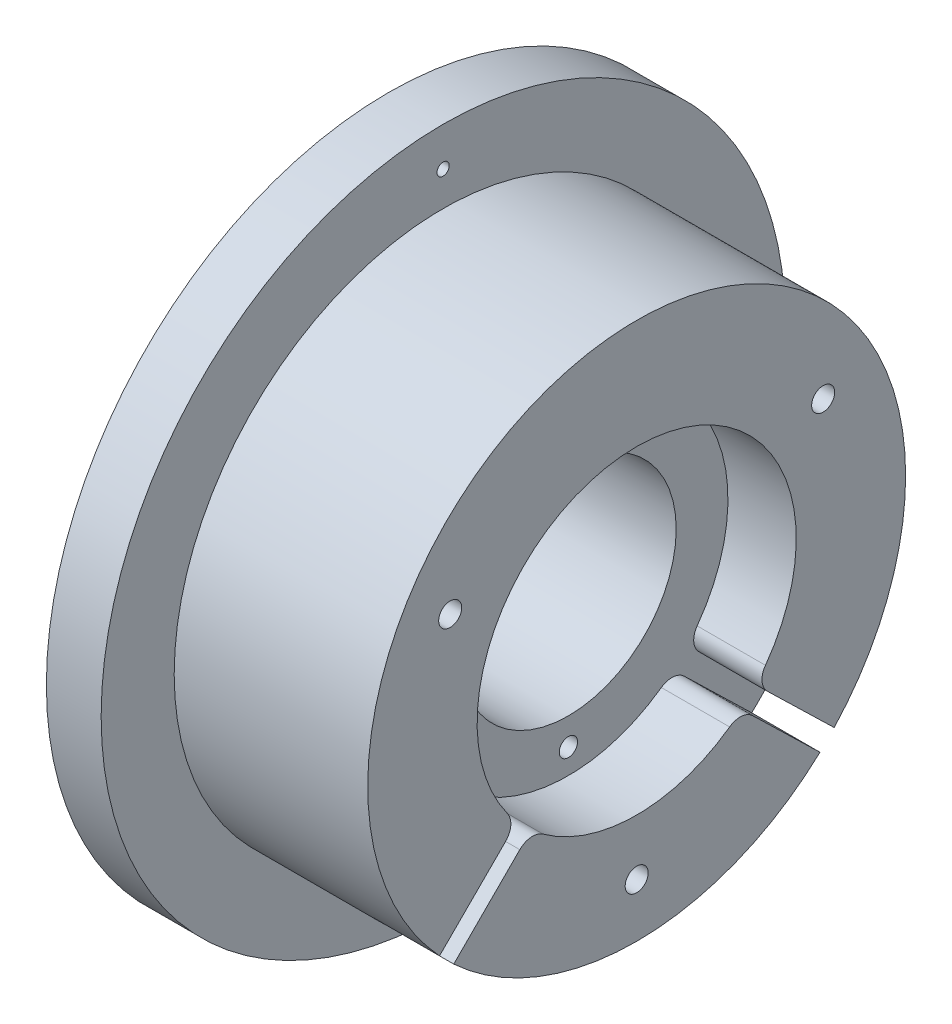
SolidWorks part; units mm, degrees
ref_plane "Front" through (0, 0, 0) normal (0, 0, 1) x (1, 0, 0)
ref_plane "Top" through (0, 0, 0) normal (0, 1, 0) x (1, 0, 0)
ref_plane "Right" through (0, 0, 0) normal (1, 0, 0) x (0, 0, -1)
sketch "Sketch1" plane through (0, 0, 0) normal (0, 0, 1) x (1, 0, 0)
  line L0 (0, 0) -> (0, 23.7871)
  line L1 (0, 23.7871) -> (3.81, 23.7871)
  line L2 (3.81, 23.7871) -> (3.81, 18.7071)
  line L3 (3.81, 18.7071) -> (17.272, 18.7071)
  line L4 (17.272, 18.7071) -> (17.272, 11.1)
  line L5 (17.272, 11.1) -> (12.522, 11.1)
  line L6 (12.522, 11.1) -> (12.522, 0)
  line L7 (12.522, 0) -> (0, 0)
  line L8 (12.522, 7.5) -> (0, 7.5)
  dimension "D1" = 23.7871
  dimension "D2" = 3.81
  dimension "D3" = 13.462
  dimension "D4" = 4.75
  dimension "D5" = 11.1
  dimension "D6" = 18.7071
  dimension "D7" = 7.5
revolve "Revolve1" add sketch "Sketch1" angle 360 about L7 region at (7.424, 14.2406, 0)
sketch "Sketch2" plane through (17.272, 0, 0) normal (1, 0, 0) x (0, 0, -1)
  line L0 (0, 0) -> (-13.2279, -13.2279) construction
  line L1 (0, 0) -> (0, -18.7071) construction
  line L2 (0.3171, 0.3268) -> (13.7426, -12.7005)
  line L3 (-13.7229, -12.7329) -> (-12.7329, -13.7229)
  line L4 (-13.7229, -12.7329) -> (-0.495, 0.495)
  line L5 (-0.495, 0.495) -> (0.495, -0.495)
  line L6 (0.495, -0.495) -> (-12.7329, -13.7229)
  line L7 (12.7677, -13.7053) -> (13.7426, -12.7005)
  line L8 (12.7677, -13.7053) -> (-0.6578, -0.6779)
  line L9 (-0.6578, -0.6779) -> (0.3171, 0.3268)
  circle A0 centre (0, 0) radius 18.7071 construction
  circle A1 centre (-12.9709, 7.4887) radius 0.315
  circle A2 centre (12.9709, 7.4888) radius 0.315
  circle A3 centre (0, 0) radius 18.7071 construction
  circle A4 centre (0, -14.9775) radius 0.315
  point P6 (0, 0)
  point P14 (-13.2279, -13.2279)
  circle M8 centre (0, 0) radius 18.7071
  circle M9 centre (0, 0) radius 11.1
  dimension "D4" = 0.63
  dimension "D1" = 45
  dimension "D2" = 1.4
  dimension "D3" = 14.9775
  dimension "D5" = 3
  dimension "D6" = 2
extrude "Cut-Extrude1" cut sketch "Sketch2" against normal up to surface (4.75 mm away) contours L8 L9 L5 L4 L6 M9 | L6 L4 M9 M8 | L8 L2 M8 M9 | L9 L5 L6 L8 L2 M9 | A4 | A1 | A2 region at (17.272, -4.188, -3.9796) region at (17.272, -10.5487, -10.5196) region at (17.272, -4.068, 4.0898) region at (17.272, -10.5343, 10.5343) region at (17.272, 7.4887, 12.9709) region at (17.272, 7.4888, -12.9709) region at (17.272, -14.9775, 0) up to face at (12.522, 0, -7.5)
sketch "Sketch3" plane through (3.81, 0, 0) normal (1, 0, 0) x (0, 0, -1)
  line L0 (0, 0) -> (0, 21.082) construction
  circle A0 centre (0, 21.082) radius 0.425
  dimension "D1" = 0.85
  dimension "D2" = 21.082
extrude "Cut-Extrude2" cut sketch "Sketch3" against normal through all
sketch "Sketch4" plane through (12.522, 0, 0) normal (1, 0, 0) x (0, 0, -1)
  line L0 (0, -9.375) -> (0, 9.375) construction
  circle A0 centre (0, 9.375) radius 0.635
  circle A1 centre (0, -9.375) radius 0.635
  point P6 (0, 0)
  dimension "D2" = 1.27
  dimension "D1" = 18.75
extrude "Cut-Extrude3" cut sketch "Sketch4" against normal through all
fillet "Fillet1" radius 1.25 4 edges at (14.897, -7.3383, 8.3282) (14.897, -8.3282, 7.3383) (14.897, -8.3798, -7.2794) (14.897, -7.3966, -8.2765)
hole_wizard "M2x0.4 Tapped Hole1" positions "3DSketch2" profile "Sketch5" tap size "M2x0.4" standard "ANSI Metric"
sketch3d "3DSketch2"
  line L0 (12.522, 7.4887, 12.9709) -> (17.272, 7.4887, 12.9709) construction
  line L1 (12.522, 7.4888, -12.9709) -> (17.272, 7.4888, -12.9709) construction
  line L2 (12.522, -14.9775, 0) -> (17.272, -14.9775, 0) construction
  point P0 (17.272, 7.4887, 12.9709)
  point P4 (17.272, 7.4888, -12.9709)
  point P8 (17.272, -14.9775, 0)
sketch "Sketch5" plane through (17.272, 7.4887, 12.9709) normal (0, 1, 0) x (0, 0, -1)
  line L0 (0, 0) -> (0, 7.9807)
  line L1 (0, 7.9807) -> (0.8, 7.5)
  line L2 (0.8, 7.5) -> (0.8, 0)
  line L5 (0.8, 0) -> (0, 0)
  line L10 (0, 7.9807) -> (-0.8, 7.5) construction
  line L11 (0, -6.35) -> (0, 107.95) construction
  dimension "Tap Drill Dia." = 1.6
  dimension "Tap Drill Depth" = 7.5
  dimension "Drill Angle" = 118
cosmetic thread "Hole Thread1" parameters "D1"=4, "D2"=2
cosmetic thread "Hole Thread2" parameters "D1"=4, "D2"=2
cosmetic thread "Hole Thread3" parameters "D1"=4, "D2"=2
